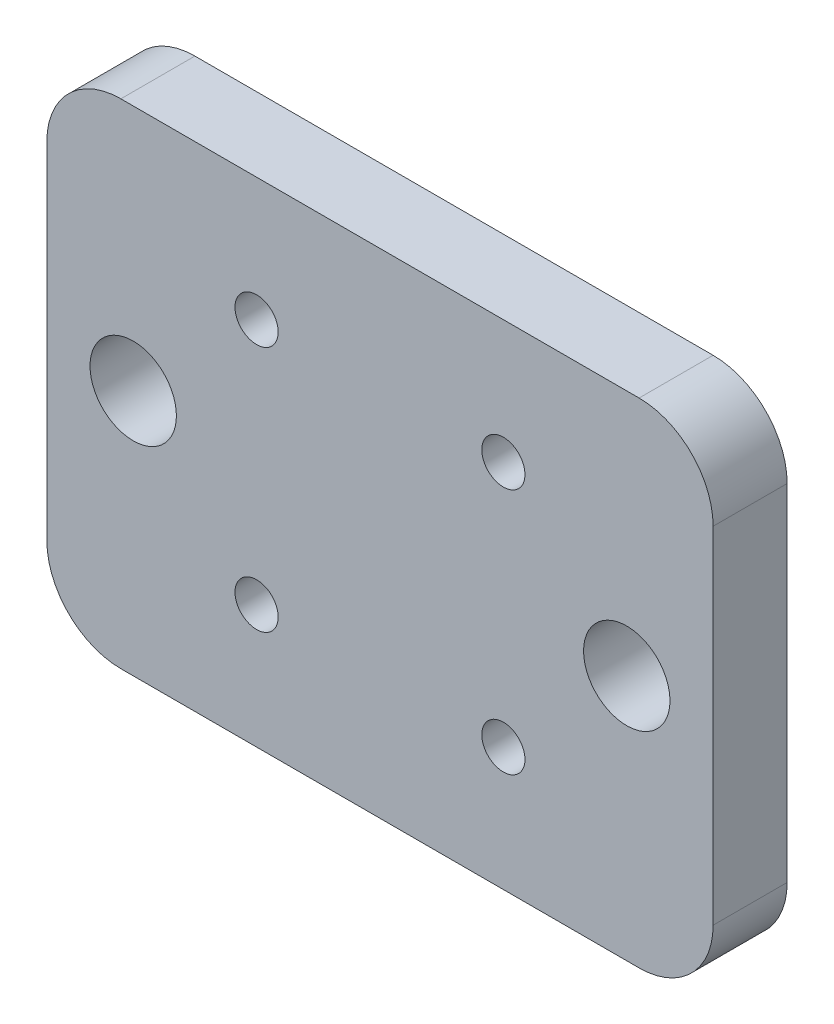
SolidWorks part; units mm, degrees
ref_plane "Plan de face" through (0, 0, 0) normal (0, 0, 1) x (1, 0, 0)
ref_plane "Plan de dessus" through (0, 0, 0) normal (0, 1, 0) x (1, 0, 0)
ref_plane "Plan de droite" through (0, 0, 0) normal (1, 0, 0) x (0, 0, -1)
sketch "Esquisse1" plane through (0, 0, 0) normal (0, 0, 1) x (1, 0, 0)
  line L1 (0, 0) -> (54, 0)
  line L2 (0, 0) -> (0, 40)
  line L3 (0, 40) -> (54, 40)
  line L4 (54, 0) -> (54, 40)
  dimension "D1" = 54
  dimension "D2" = 40
extrude "Boss.-Extru.1" add sketch "Esquisse1" along normal blind 6
sketch "Esquisse2" plane through (0, 0, 6) normal (0, 0, 1) x (1, 0, 0)
  line L0 (27, 0) -> (27, 40) construction
  line L1 (0, 0) -> (54, 0) construction
  line L2 (54, 40) -> (0, 40) construction
  line L3 (54, 20) -> (0, 20) construction
  line L4 (54, 0) -> (54, 40) construction
  line L5 (0, 40) -> (0, 0) construction
  circle A0 centre (17, 30) radius 1.75
  circle A1 centre (37, 30) radius 1.75
  circle A2 centre (37, 10) radius 1.75
  circle A3 centre (17, 10) radius 1.75
  circle A4 centre (7, 20) radius 3.5
  circle A5 centre (47, 20) radius 3.5
  dimension "D1" = 3.5
  dimension "D3" = 20
  dimension "D4" = 7
  dimension "D2" = 20
  dimension "D5" = 40
extrude "Enlèv. mat.-Extru.1" cut sketch "Esquisse2" against normal through all both and the other way through all
fillet "Congé1" radius 6 4 edges at (54, 40, 3) (54, 0, 3) (0, 0, 3) (0, 40, 3)
